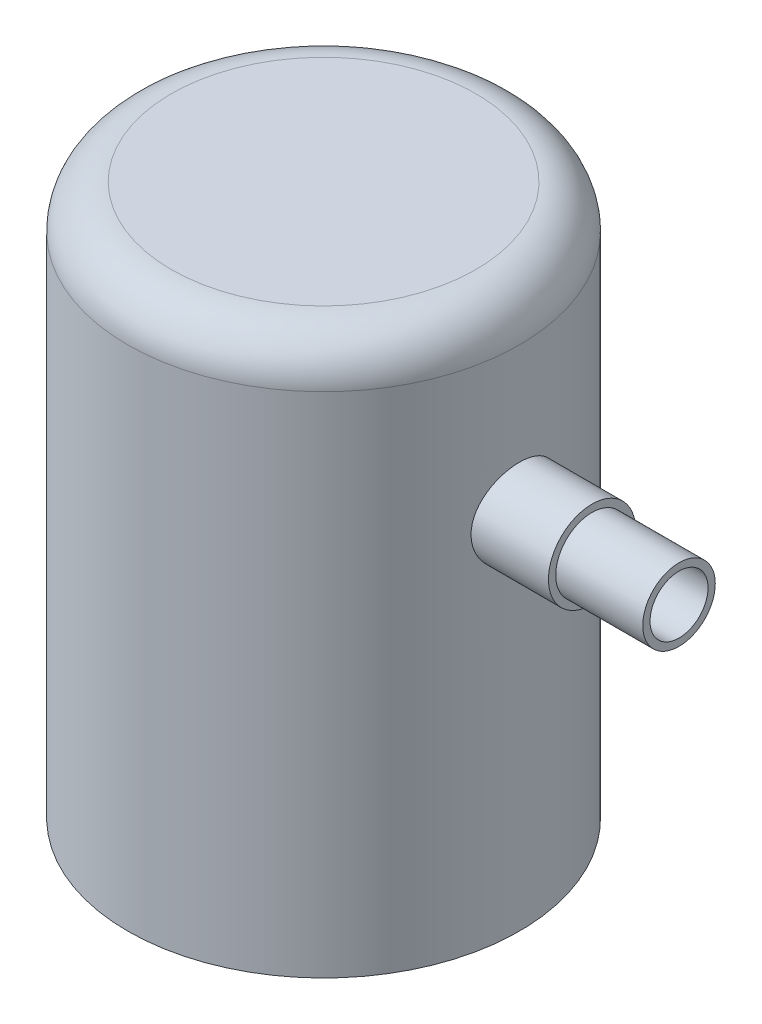
SolidWorks part; units mm, degrees
material "Copper"
ref_plane "Front Plane" through (0, 0, 0) normal (0, 0, 1) x (1, 0, 0)
ref_plane "Top Plane" through (0, 0, 0) normal (0, 1, 0) x (1, 0, 0)
ref_plane "Right Plane" through (0, 0, 0) normal (1, 0, 0) x (0, 0, -1)
sketch "Sketch1" plane through (0, 0, 0) normal (0, 1, 0) x (1, 0, 0)
  circle A0 centre (0, 0) radius 13.5
  dimension "D1" = 27
extrude "Boss-Extrude1" add sketch "Sketch1" along normal blind 38
fillet "Fillet1" radius 3 1 edges at (0, 38, 13.5)
sketch "Sketch2" plane through (0, 0, 0) normal (0, -1, 0) x (1, 0, 0)
  line L0 (0, 0) -> (-13.5, 0)
  line L1 (-13.5, 0) -> (0, 0)
  line L2 (0, 11.5) -> (0, 13.5)
  line L3 (0, 13.5) -> (0, 11.5)
  circle A0 centre (0, 0) radius 13.5 construction
  circle A1 centre (0, 10) radius 1.5
  circle A2 centre (0, -10) radius 1.5
  circle A3 centre (7, 0) radius 3.5
  circle A4 centre (-6, 0) radius 6
  dimension "D3" = 3
  dimension "D4" = 3
  dimension "D7" = 12
  dimension "D8" = 7
  dimension "D1" = 10
  dimension "D2" = 10
  dimension "D5" = 13
  dimension "D6" = 7
extrude "Cut-Extrude5" cut sketch "Sketch2" against normal blind 1 contours L0 A4 | L0 A4 | A1 | A3 | A2 region at (-6, 0, -2.5465) region at (-6, 0, 2.5465) region at (0, 0, 10) region at (0, 0, -10) region at (7, 0, 0)
cosmetic thread "Cosmetic Thread1" parameters "D2"=9
cosmetic thread "Cosmetic Thread2" parameters "D2"=9
sketch "Sketch7" plane through (0, 0, 0) normal (0, -1, 0) x (1, 0, 0)
  circle A0 centre (-6, 0) radius 6
  dimension "D1" = 12
extrude "Cut-Extrude6" cut sketch "Sketch7" against normal blind 27
sketch "Sketch8" plane through (0, 0, 0) normal (0, -1, 0) x (1, 0, 0)
  circle A0 centre (7, 0) radius 3.5
  dimension "D1" = 7
extrude "Cut-Extrude7" cut sketch "Sketch8" against normal blind 32
sketch "Sketch9" plane through (0, 0, 0) normal (0, -1, 0) x (1, 0, 0)
  circle A0 centre (0, 10) radius 1.5
  circle A1 centre (0, -10) radius 1.5
  dimension "D1" = 3
  dimension "D2" = 3
extrude "Cut-Extrude8" cut sketch "Sketch9" against normal blind 3
hole_wizard "Ø4.0mm Dowel Hole1" positions "3DSketch1" profile "Sketch11" hole size "Ø4.0" standard "ISO"
sketch3d "3DSketch1"
  point P0 (13.5, 25, 0)
  dimension "D1" = 25
sketch "Sketch11" plane through (13.5, 25, 0) normal (0, 1, 0) x (0, 0, -1)
  line L0 (0, 0) -> (0, 21.2017)
  line L1 (0, 21.2017) -> (2, 20)
  line L2 (2, 20) -> (2, 0)
  line L5 (2, 0) -> (0, 0)
  line L10 (0, 21.2017) -> (-2, 20) construction
  line L11 (0, -6.35) -> (0, 107.95) construction
  dimension "Hole Dia." = 4
  dimension "Hole Depth" = 20
  dimension "Drill Angle" = 118
ref_plane "Plane1" through (24.5, 0, 0) normal (1, 0, 0) x (0, 0, -1)
sketch "Sketch12" plane through (24.5, 0, 0) normal (1, 0, 0) x (0, 0, -1)
  circle A0 centre (0, 25) radius 3
  circle A1 centre (0, 25) radius 2
  dimension "D1" = 6
  dimension "D2" = 4
extrude "Boss-Extrude2" add sketch "Sketch12" against normal up to next
sketch "Sketch13" plane through (24.5, 0, 0) normal (1, 0, 0) x (0, 0, -1)
  circle A0 centre (0, 25) radius 3
  circle A1 centre (0, 25) radius 2.5
  dimension "D1" = 6
  dimension "D2" = 5
extrude "Cut-Extrude9" cut sketch "Sketch13" against normal blind 6
cosmetic thread "Cosmetic Thread4" parameters "D1"=6, "D2"=4
